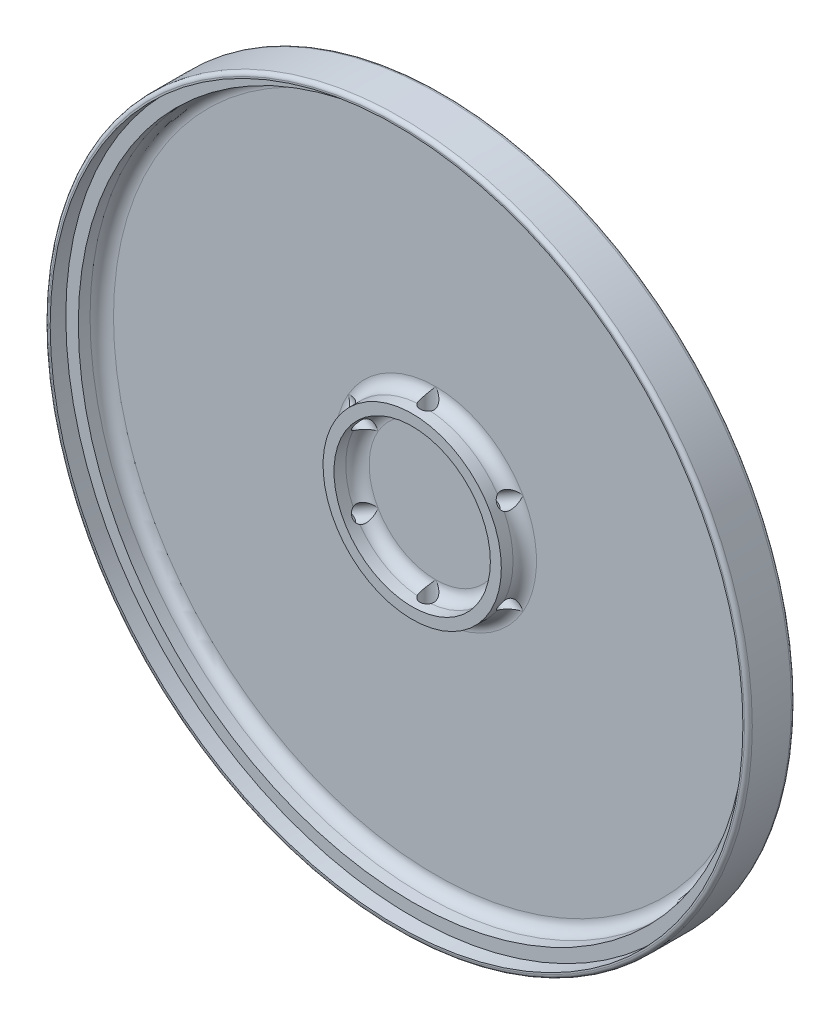
SolidWorks part; units mm, degrees
note: The reader was unsure of these and kept them because the rebuilt part matched: shared geometry of "Sketch1<3>", "Sketch1<4>", "Sketch1<5>".
ref_plane "Front Plane" through (0, 0, 0) normal (0, 0, 1) x (1, 0, 0)
ref_plane "Top Plane" through (0, 0, 0) normal (0, 1, 0) x (1, 0, 0)
ref_plane "Right Plane" through (0, 0, 0) normal (1, 0, 0) x (0, 0, -1)
sketch "Sketch1" plane through (0, 0, 0) normal (0, 0, 1) x (1, 0, 0)
  circle A0 centre (0, 0) radius 90
  circle A1 centre (0, 0) radius 88.6
  circle A2 centre (0, 0) radius 85.4
  circle A3 centre (0, 0) radius 20
  circle A4 centre (0, 0) radius 22.8
  dimension "D1" = 180
  dimension "D5" = 40
  dimension "D2" = 1.4
  dimension "D3" = 3.2
  dimension "D4" = 2.8
extrude "Boss-Extrude1" add sketch "Sketch1" against normal blind 2 contours A2 A4 | A1 A2 | A0 A1 | A3 | A4 A3
extrude "Boss-Extrude2" add sketch "Sketch1<3>" along normal blind 10 contours A0 A1
sketch "Sketch1<3>" plane through (0, 0, 0) normal (0, 0, 1) x (1, 0, 0) same geometry as "Sketch1"
extrude "Boss-Extrude3" add sketch "Sketch1<4>" along normal blind 6 contours A1 A2
sketch "Sketch1<4>" plane through (0, 0, 0) normal (0, 0, 1) x (1, 0, 0) same geometry as "Sketch1"
extrude "Boss-Extrude4" add sketch "Sketch1<5>" along normal blind 6 contours A4 A3
sketch "Sketch1<5>" plane through (0, 0, 0) normal (0, 0, 1) x (1, 0, 0) same geometry as "Sketch1"
sketch "Sketch2" plane through (0, 0, 0) normal (0, 1, 0) x (1, 0, 0)
  line L2 (-20, 0) -> (20, 0) construction
  circle A0 centre (0, -2) radius 2
  point P2 (0, 0)
  point P3 (0, -4.1041)
  point P6 (-33.9456, -3)
  dimension "D1" = 4
extrude "Cut-Extrude3" cut sketch "Sketch2" against normal up to next and the other way up to next
fillet "Fillet1" radius 3 1 edges at (85.4, 0, 0)
fillet "Fillet2" radius 3 8 edges at (20, 0, 0) (-22.8, 0, 0) (0.2176, 22.799, 3.9881) (0.2198, 19.9988, 3.9879) (-20, 0, 0) (22.8, 0, 0) (0, -22.8, 4) (0, -20, 4)
fillet "Fillet3" radius 1 1 edges at (90, 0, -2)
fillet "Fillet4" radius 1 1 edges at (90, 0, 10)
pattern_circular "CirPattern1" count 3 over 360 about axis through (0, 0, 6) along (0, 0, -1) of "Cut-Extrude3"
